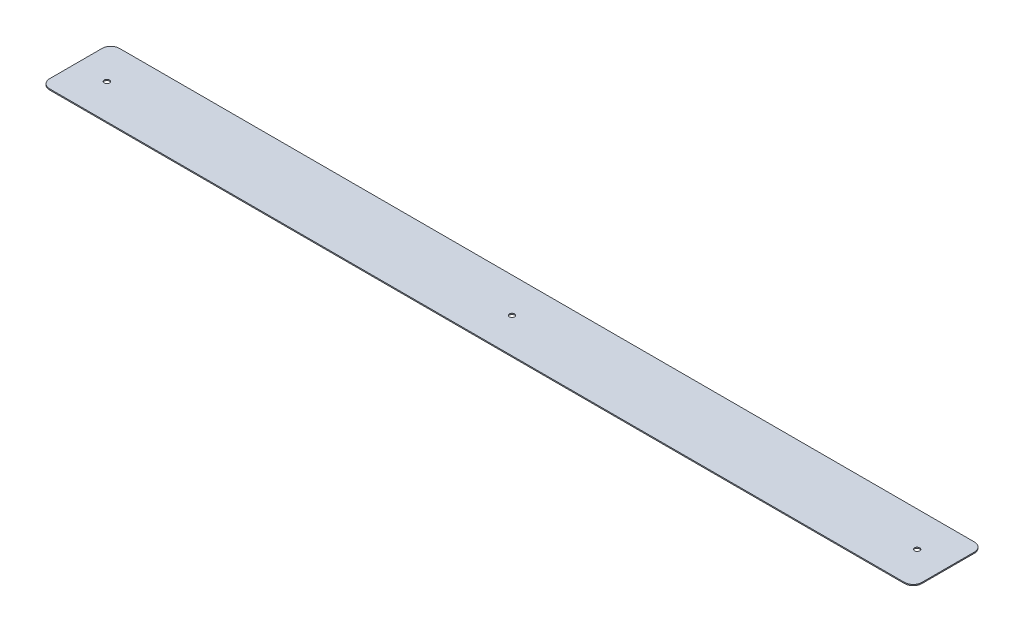
SolidWorks part; units mm, degrees
ref_plane "Front Plane" through (0, 0, 0) normal (0, 0, 1) x (1, 0, 0)
ref_plane "Top Plane" through (0, 0, 0) normal (0, 1, 0) x (1, 0, 0)
ref_plane "Right Plane" through (0, 0, 0) normal (1, 0, 0) x (0, 0, -1)
sketch "Sketch1" plane through (0, 0, 0) normal (0, 1, 0) x (1, 0, 0)
  line L1 (-316.7761, -25.4) -> (316.7761, -25.4)
  line L2 (-316.7761, -25.4) -> (-316.7761, 25.4)
  line L3 (-316.7761, 25.4) -> (316.7761, 25.4)
  line L4 (316.7761, -25.4) -> (316.7761, 25.4)
  line L5 (-316.7761, -25.4) -> (316.7761, 25.4) construction
  line L6 (-316.7761, 25.4) -> (316.7761, -25.4) construction
  point P0 (0, 0)
  dimension "D1" = 50.8
  dimension "D2" = 633.5522
extrude "Boss-Extrude1" add sketch "Sketch1" along normal blind 0.7937
fillet "Fillet1" radius 6.35 4 edges at (-316.7761, 0.3969, -25.4) (-316.7761, 0.3969, 25.4) (316.7761, 0.3969, -25.4) (316.7761, 0.3969, 25.4)
hole_wizard "#6 Clearance Hole1" positions "Sketch2" profile "Sketch3" hole size "#6" standard "ANSI Inch" end condition through all
sketch "Sketch2" plane through (0, 0.7937, 0) normal (0, 1, 0) x (1, 0, 0)
  line L0 (-316.7761, 0) -> (316.7761, 0) construction
  line L1 (-316.7761, 19.05) -> (-316.7761, -19.05) construction
  line L2 (316.7761, -19.05) -> (316.7761, 19.05) construction
  point P8 (0, 0)
  point P12 (-294.2568, 0)
  point P14 (294.2568, 0)
  dimension "D1" = 294.2568
  dimension "D2" = 294.2568
sketch "Sketch3" plane through (294.2568, 0.7937, 0) normal (1, 0, 0) x (0, 0, 1)
  line L0 (0, 0) -> (0, 0.7937)
  line L1 (0, 0.7937) -> (1.8986, 0.7937)
  line L2 (1.8986, 0.7937) -> (1.8986, 0)
  line L5 (1.8986, 0) -> (0, 0)
  line L11 (0, -6.35) -> (0, 107.95) construction
  dimension "Thru Hole Dia." = 3.7973
  dimension "Thru Hole Depth" = 0.7937
